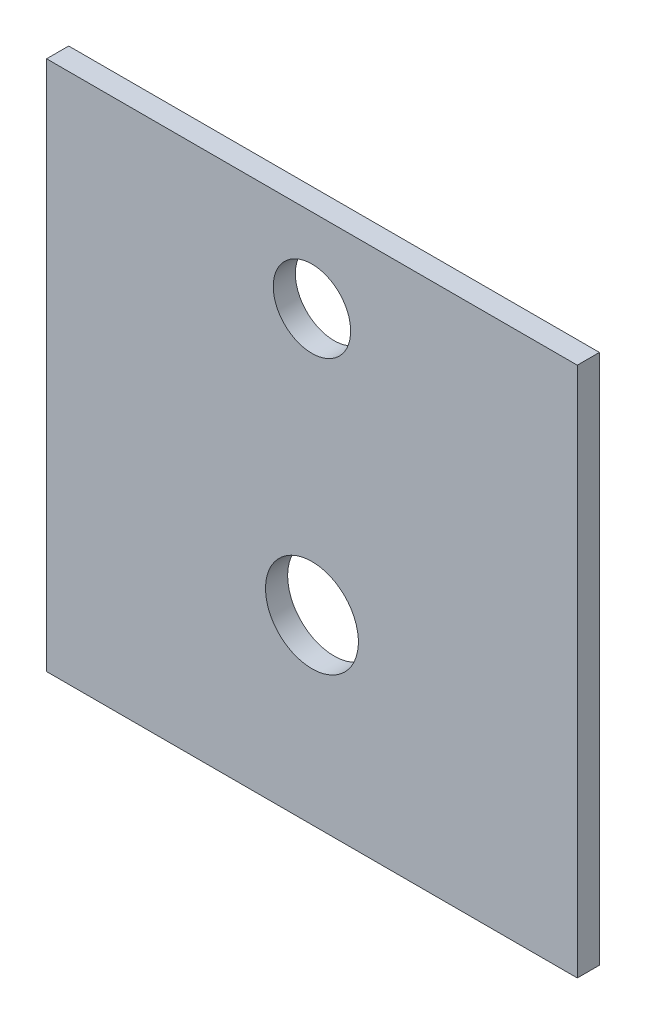
SolidWorks part; units mm, degrees
material "Plain Carbon Steel"
ref_plane "Front Plane" through (0, 0, 0) normal (0, 0, 1) x (1, 0, 0)
ref_plane "Top Plane" through (0, 0, 0) normal (0, 1, 0) x (1, 0, 0)
ref_plane "Right Plane" through (0, 0, 0) normal (1, 0, 0) x (0, 0, -1)
sketch "Sketch1" plane through (0, 0, 0) normal (0, 0, 1) x (1, 0, 0)
  line L1 (0, 0) -> (24, 0)
  line L2 (0, 0) -> (0, 24)
  line L3 (0, 24) -> (24, 24)
  line L4 (24, 0) -> (24, 24)
  dimension "D1" = 24
  dimension "D2" = 24
base flange "Base-Flange1" sketch "Sketch1" thickness 1 reverse thickness direction no parameters "D1"=1.6
sketch "Sketch4" plane through (0, 0, -1) normal (0, 0, -1) x (-1, 0, 0)
  line L0 (-12, 20.2108) -> (-12, 8.2108)
  circle A0 centre (-12, 20.2108) radius 1.75
  circle A1 centre (-12, 8.2108) radius 2.1
  dimension "D1" = 12
  dimension "D2" = 4.2
extrude "Cut-Extrude1" cut sketch "Sketch4" against normal blind 10
sketch "Bend-Lines1" [suppressed]
sketch "Bounding-Box1" [suppressed]
sheet metal parameters "Sheet-Metal8" thickness 1 parameters "D1"=1.6
flat pattern "Flat-Pattern8" [suppressed]
sketch "Bend-Lines2" plane through (0, 0, 0) normal (0, 1, 0) x (1, 0, 0)
sketch3d "Bounding-Box2" [suppressed]
  line L0 (0, 0, 0) -> (24, 0, 0) construction
  line L1 (0, 24, 0) -> (24, 24, 0) construction
  line L2 (0, 0, 0) -> (0, 24, 0) construction
  line L3 (24, 0, 0) -> (24, 24, 0) construction
sheet metal parameters "Sheet-Metal10" thickness 1 parameters "D1"=1.6
flat pattern "Flat-Pattern8"
sketch "Bend-Lines2" plane through (0, 0, 0) normal (0, 1, 0) x (1, 0, 0)
sketch3d "Bounding-Box2" [suppressed]
  line L0 (0, 0, 0) -> (24, 0, 0) construction
  line L1 (0, 24, 0) -> (24, 24, 0) construction
  line L2 (0, 0, 0) -> (0, 24, 0) construction
  line L3 (24, 0, 0) -> (24, 24, 0) construction
